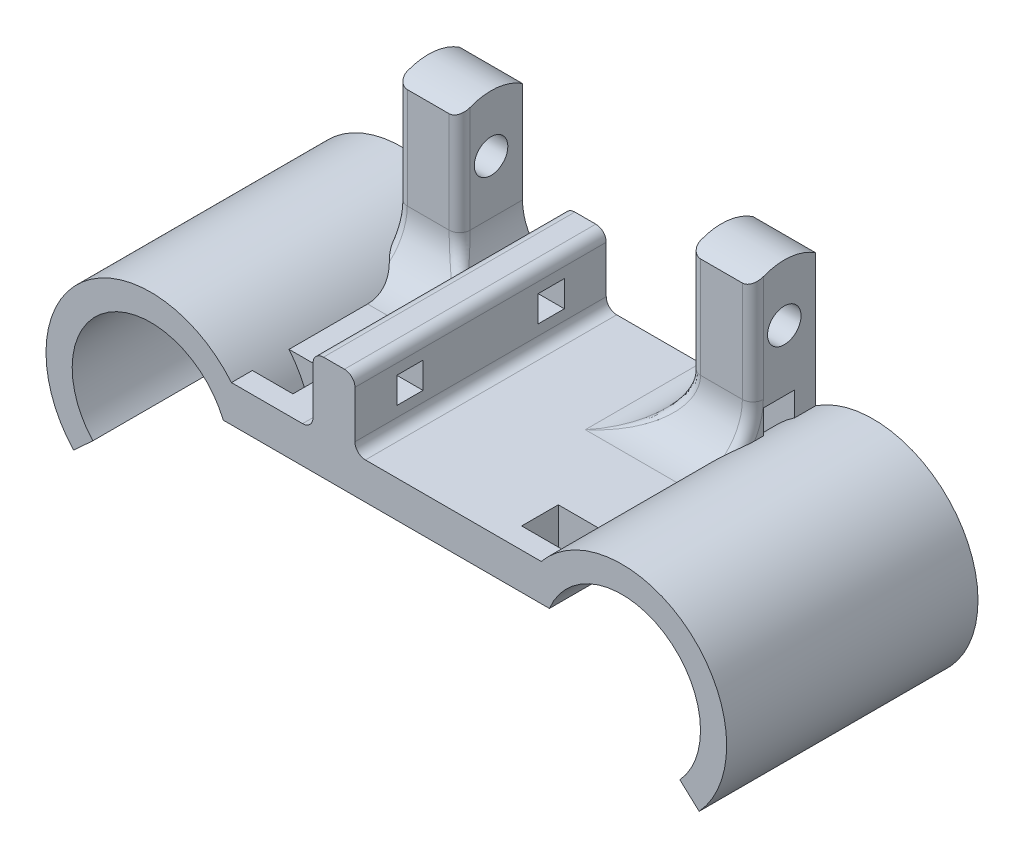
SolidWorks part; units mm, degrees
ref_plane "Front" through (0, 0, 0) normal (0, 0, 1) x (1, 0, 0)
ref_plane "Top" through (0, 0, 0) normal (0, 1, 0) x (1, 0, 0)
ref_plane "Right" through (0, 0, 0) normal (1, 0, 0) x (0, 0, -1)
sketch "Sketch1" plane through (0, 0, 0) normal (0, 0, 1) x (1, 0, 0)
  line L0 (-28.0296, -7.9371) -> (-22.5, -2.8701) construction
  line L1 (-22.5, -2.8701) -> (-15.5709, 0) construction
  line L2 (-22.5, -2.8701) -> (-22.5, 4.6299) construction
  arc A0 (-15.5709, 0) -> (-28.0296, -7.9371) centre (-22.5, -2.8701) ccw
  dimension "D2" = 7.5
  dimension "D1" = 22.5
  dimension "D3" = 200
  dimension "D4" = 67.5
extrude "Extrude-LM8UU Cup" add sketch "Sketch1" along normal blind 24 thin thin type one direction wall 2.5
sketch "Sketch2" plane through (0, 0, 0) normal (0, 0, 1) x (1, 0, 0)
  line L0 (0, 0) -> (-15.5709, 0)
extrude "Extrude-Straight" add sketch "Sketch2" along normal through all thin thin type one direction wall 3.5
sketch "Sketch5" plane through (0, 0, 24) normal (0, 0, 1) x (1, 0, 0)
  line L0 (0, 0) -> (-15.5709, 0) construction
  line L1 (-12.9207, 0) -> (-10.9207, 0)
  line L2 (-10.9207, 0) -> (-10.9207, 3.5)
  line L3 (0, 3.5) -> (-14.7915, 3.5) construction
  line L4 (-10.9207, 3.5) -> (-14.7915, 3.5)
  arc A0 (-14.7915, 3.5) -> (-12.9207, 0) centre (-22.5, -2.8701) cw
  arc A1 (-14.7915, 3.5) -> (-29.8728, -9.626) centre (-22.5, -2.8701) ccw construction
  dimension "D1" = 2
extrude "Cut-Upper Zip Tie" cut sketch "Sketch5" against normal blind 3.5 from offset 2 offset against normal yes
mirror "Mirror-Cup And Straight" about plane through (0, 0, 0) normal (1, 0, 0) of "Extrude-LM8UU Cup", "Extrude-Straight", "Cut-Upper Zip Tie"
sketch "Sketch6" plane through (0, 0, 0) normal (1, 0, 0) x (0, 0, -1)
  line L1 (-6, 3.5) -> (0, 3.5)
  line L2 (-6, 3.5) -> (-6, 15.6299)
  line L3 (-6, 15.6299) -> (0, 15.6299)
  line L4 (0, 3.5) -> (0, 15.6299)
  dimension "D1" = 6
  dimension "D2" = 18.5
extrude "Boss-Rod Attachments" add sketch "Sketch6" along normal blind 6 from offset 11
sketch "Sketch7" plane through (11, 0, 0) normal (-1, 0, 0) x (0, 0, 1)
  line L0 (3, 15.6299) -> (3, 13.6299) construction
  line L1 (0, 15.6299) -> (6, 15.6299) construction
  circle A0 centre (3, 13.6299) radius 1.6
  dimension "D2" = 3.2
  dimension "D1" = 16.5
extrude "Cut-Rod Screw Hole" cut sketch "Sketch7" against normal through all
sketch "Sketch8" plane through (11, 0, 0) normal (-1, 0, 0) x (0, 0, 1)
  line L0 (0, 15.6299) -> (6, 15.6299)
  line L1 (0, 15.6299) -> (0, 18.1299)
  line L2 (0, 18.1299) -> (6, 18.1299) construction
  line L3 (6, 18.1299) -> (6, 15.6299)
  arc A0 (0, 18.1299) -> (6, 18.1299) centre (3, 13.6299) cw
  dimension "D1" = 2.5
extrude "Boss-Rod Round End" add sketch "Sketch8" against normal up to surface (6 mm away) up to face at (17, 13.6299, 4.6)
mirror "Mirror-Rod Attachment" about plane through (0, 0, 0) normal (1, 0, 0) of "Boss-Rod Round End", "Cut-Rod Screw Hole", "Boss-Rod Attachments"
fillet "Fillet1" radius 5 4 edges at (12.8957, 3.5, 6) (-12.8957, 3.5, 6) (-11, 3.5, 3) (11, 3.5, 3)
fillet "Fillet2" radius 1 8 edges at (9.5355, 4.9645, 7.4645) (-9.5355, 4.9645, 7.4645) (11, 13.3149, 6) (-11, 13.3149, 6) (17, 6.9079, 6.2603) (-17, 13.3149, 6) (17, 13.3149, 6) (-17, 6.9079, 6.2603)
sketch "Sketch9" plane through (0, 0, 0) normal (1, 0, 0) x (0, 0, -1)
  line L1 (0, 0) -> (-24, 0)
  line L2 (0, 0) -> (0, 10)
  line L3 (0, 10) -> (-24, 10)
  line L4 (-24, 0) -> (-24, 10)
  dimension "D1" = 10
extrude "Boss-Spectra Mount" add sketch "Sketch9" against normal blind 4 from offset 3 offset against normal yes
sketch "Sketch10" plane through (-7, 0, 0) normal (-1, 0, 0) x (0, 0, 1)
  line L1 (17.5, 8) -> (20, 8)
  line L2 (17.5, 8) -> (17.5, 5.5)
  line L3 (17.5, 5.5) -> (20, 5.5)
  line L4 (20, 8) -> (20, 5.5)
  line L5 (24, 10) -> (24, 3.5) construction
  line L6 (11, 3.5) -> (24, 3.5) construction
  dimension "D1" = 2.5
  dimension "D2" = 2
  dimension "D3" = 4
extrude "Cut-Spectra Hole" cut sketch "Sketch10" against normal up to surface (4 mm away) up to face at (-3, 6.75, 12)
pattern_linear "LPattern-Spectra Holes" count 1 spacing 4 along (0, 1, 0) count 2 spacing 13.5 along (0, 0, -1) of "Cut-Spectra Hole"
fillet "Fillet3" radius 1 7 edges at (-7, 3.601, 4.9) (-7, 3.5175, 10.5819) (-7, 3.5, 17.5) (-3, 3.5, 12) (-3, 10, 12) (-7, 10, 12)
sketch "Sketch11" plane through (0, 0, 0) normal (0, 0, -1) x (-1, 0, 0)
  line L0 (-17, 5.4815) -> (-17, 18.1299) construction
  line L1 (-15.5709, 0) -> (15.5709, 0) construction
  line L2 (-17, 7.7952) -> (-21.7869, 7.1044)
  line L3 (-12.9207, 0) -> (-10.8483, 0)
  arc A0 (-12.9207, 0) -> (-14.7915, 3.5) centre (-22.5, -2.8701) ccw construction
  arc A1 (-12.9207, 0) -> (-21.7869, 7.1044) centre (-22.5, -2.8701) ccw
  arc A2 (-10.8483, 0) -> (-17, 7.7952) centre (-22.5, -2.8701) ccw
  arc A3 (-11.0049, 0.574) -> (-21.6442, 9.0993) centre (-22.5, -2.8701) ccw construction
  arc A4 (-17, 5.4815) -> (-29.8728, -9.626) centre (-22.5, -2.8701) ccw construction
  dimension "D1" = 2
extrude "Cut-Lower Zip Tie" cut sketch "Sketch11" against normal blind 3 from offset 2 offset against normal yes
mirror "Mirror-Lower Zip Tie" about plane through (0, 0, 0) normal (1, 0, 0) of "Cut-Lower Zip Tie"
sketch "Sketch13" plane through (0, 0, 0) normal (0, 0, -1) x (-1, 0, 0)
  circle A0 centre (0, 13) radius 3.5
  dimension "D1" = 7
  dimension "D2" = 13
extrude "Boss-Magnet Boss" [suppressed] add sketch "Sketch13" against normal blind 3.5
sketch "Sketch12" [suppressed] plane through (0, 0, 0) normal (0, 0, -1) x (-1, 0, 0)
  circle A0 centre (0, 13) radius 2.5
  arc A1 (2.8723, 15) -> (0, 9.5) centre (0, 13) ccw construction
  dimension "D1" = 5
extrude "Cut-Magnet Slot" [suppressed] cut sketch "Sketch12" against normal blind 2.5
